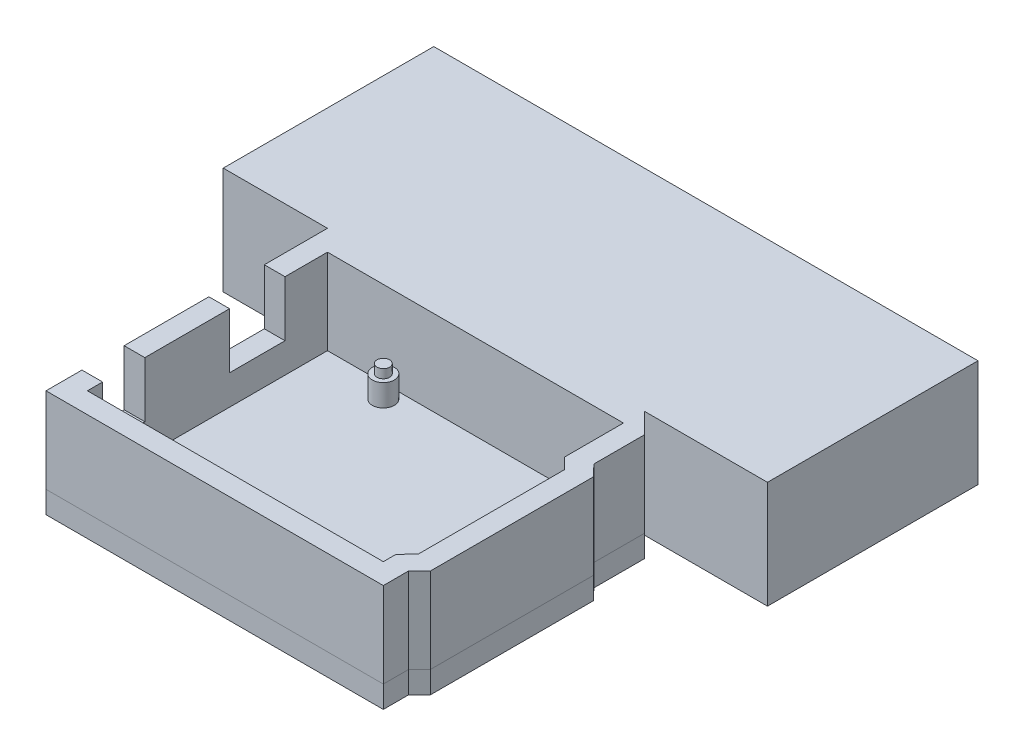
SolidWorks part; units mm, degrees
ref_plane "Front Plane" through (0, 0, 0) normal (0, 0, 1) x (1, 0, 0)
ref_plane "Top Plane" through (0, 0, 0) normal (0, 1, 0) x (1, 0, 0)
ref_plane "Right Plane" through (0, 0, 0) normal (1, 0, 0) x (0, 0, -1)
sketch "Sketch2" plane through (0, 0, 0) normal (0, 1, 0) x (1, 0, 0)
  line L3 (12.5897, 24.8031) -> (15.0697, 22.2631)
  line L4 (15.0697, 22.2631) -> (15.0697, -10.5029)
  line L5 (15.0697, -10.5029) -> (12.5897, -13.0429)
  line L6 (12.5897, -13.0429) -> (12.5897, -15.5829)
  line L7 (12.5897, -15.5829) -> (-53.4803, -15.5829)
  line L8 (-53.4803, -15.5829) -> (-53.4803, 37.7956)
  line L9 (-58.7803, 43.0956) -> (13.2202, 43.0956)
  line L10 (13.2202, 43.0956) -> (17.8897, 38.4261)
  line L11 (17.8897, 38.4261) -> (17.8897, 26.9614)
  line L12 (17.8897, 26.9614) -> (20.3697, 24.4214)
  line L13 (20.3697, 24.4214) -> (20.3697, -12.6612)
  line L14 (20.3697, -12.6612) -> (17.8897, -15.2012)
  line L15 (17.8897, -15.2012) -> (17.8897, -20.8829)
  line L16 (17.8897, -20.8829) -> (-58.7803, -20.8829)
  line L17 (-58.7803, -20.8829) -> (-58.7803, 43.0956)
  line L20 (12.5897, 37.7956) -> (12.5897, 24.8031)
  line L21 (11.0249, 37.7956) -> (12.5897, 36.2308) construction
  line L26 (12.5897, 36.2308) -> (12.5897, 24.8031) construction
  line L27 (-53.4803, 37.7956) -> (11.0249, 37.7956) construction
  line L28 (12.5897, 37.7956) -> (-53.4803, 37.7956)
  circle A0 centre (-38.2103, 35.2171) radius 1.5875
  circle A1 centre (12.5579, 19.9653) radius 1.5875
  circle A2 centre (12.5897, -7.9629) radius 1.5875
  circle A3 centre (-39.5103, -13.0429) radius 1.5875
  dimension "D4" = 3.5499
  dimension "D5" = 32.766
  dimension "D6" = 3.5499
  dimension "D7" = 2.54
  dimension "D8" = 66.07
  dimension "D9" = 53.3785
  dimension "D11" = 135.685
  dimension "D12" = 5.3
extrude "Boss-Extrude1" add sketch "Sketch2" along normal blind 5 contours L17 L16 L15 L14 L13 L12 L11 L10 L9 L7 L8 L3 L4 L5 L6 | L8 L7 L6 L5 L4 L3 A3 A2 A1 A0 region at (-19.6729, 0, -11.0012) region at (-22.7801, 0, -42.0778)
sketch "Sketch4" plane through (0, 5, 0) normal (0, 1, 0) x (1, 0, 0)
  line L3 (12.5885, 24.8065) -> (15.0685, 22.2665)
  line L4 (15.0685, 22.2665) -> (15.0685, -10.4995)
  line L5 (15.0685, -10.4995) -> (12.5885, -13.0395)
  line L6 (12.5885, -13.0395) -> (12.5885, -15.5795)
  line L7 (12.5885, -15.5795) -> (-53.4815, -15.5795)
  line L8 (-53.4815, -15.5795) -> (-53.4815, 37.799)
  line L9 (-58.7815, 43.099) -> (13.2191, 43.099)
  line L10 (13.2191, 43.099) -> (17.8885, 38.4295)
  line L11 (17.8885, 38.4295) -> (17.8885, 26.9649)
  line L12 (17.8885, 26.9649) -> (20.3685, 24.4249)
  line L13 (20.3685, 24.4249) -> (20.3685, -12.6578)
  line L14 (20.3685, -12.6578) -> (17.8885, -15.1978)
  line L15 (17.8885, -15.1978) -> (17.8885, -20.8795)
  line L16 (17.8885, -20.8795) -> (-58.7815, -20.8795)
  line L17 (-58.7815, -20.8795) -> (-58.7815, 43.099)
  line L21 (13.1885, 25.0509) -> (15.6685, 22.5109)
  line L22 (15.6685, 22.5109) -> (15.6685, -10.7438)
  line L23 (15.6685, -10.7438) -> (13.1885, -13.2838)
  line L24 (13.1885, -13.2838) -> (13.1885, -16.1795)
  line L25 (13.1885, -16.1795) -> (-54.0815, -16.1795)
  line L26 (-54.0815, -16.1795) -> (-54.0815, 38.399)
  line L31 (13.1885, 38.399) -> (13.1885, 25.0509)
  line L32 (11.2723, 38.399) -> (13.1885, 36.4827) construction
  line L33 (11.0238, 37.799) -> (12.5885, 36.2342) construction
  line L42 (13.1885, 36.4827) -> (13.1885, 25.0509) construction
  line L43 (-54.0815, 38.399) -> (11.2723, 38.399) construction
  line L44 (-53.4815, 37.799) -> (11.0238, 37.799) construction
  line L45 (12.5885, 36.2342) -> (12.5885, 24.8065) construction
  line L46 (12.5885, 24.8065) -> (12.5897, 37.7956)
  line L47 (12.5897, 37.7956) -> (-53.4815, 37.799)
  line L48 (-54.0815, 38.399) -> (13.1885, 38.399)
  circle A0 centre (-38.2115, 35.2205) radius 1.5875
  circle A1 centre (12.5567, 19.9688) radius 1.5875
  circle A2 centre (12.5885, -7.9595) radius 1.5875
  circle A3 centre (-39.5115, -13.0395) radius 1.5875
  dimension "D3" = 3.5499
  dimension "D4" = 32.766
  dimension "D5" = 3.5499
  dimension "D6" = 2.54
  dimension "D7" = 66.07
  dimension "D8" = 53.3785
  dimension "D10" = 135.685
  dimension "D11" = 0.6
extrude "Boss-Extrude3" add sketch "Sketch4" along normal blind 10 contours L9 L10 L11 L12 L13 L14 L15 L16 L17 | L21 L22 L23 L24 L25 L26 L48 L31
sketch "Sketch5" plane through (0, 15, 0) normal (0, 1, 0) x (1, 0, 0)
  line L0 (-58.7815, -20.8795) -> (-58.7815, 43.099) construction
  line L7 (-54.0815, -16.1795) -> (-54.0815, 38.399) construction
  line L14 (-58.7815, 28.439) -> (-58.7815, 16.439)
  line L16 (-54.0815, 28.439) -> (-54.0815, 16.439)
  line L17 (-54.0815, -16.1795) -> (-54.0815, 38.399) construction
  line L37 (-58.7815, 28.439) -> (-58.7815, 28.739)
  line L38 (-58.7815, 28.739) -> (-54.0815, 28.739)
  line L39 (-54.0815, 28.439) -> (-54.0815, 28.739)
  line L41 (-58.7815, 16.439) -> (-58.7815, 16.139)
  line L42 (-58.7815, 16.139) -> (-54.0815, 16.139)
  line L43 (-54.0815, 16.439) -> (-54.0815, 16.139)
  line L49 (-58.7815, -3.421) -> (-58.7815, -12.4107)
  line L59 (-54.0815, -3.421) -> (-54.0815, -12.4107)
  line L60 (-58.7815, -12.4107) -> (-58.7815, -12.7107)
  line L62 (-58.7815, -3.421) -> (-58.7815, -3.121)
  line L63 (-58.7815, -3.121) -> (-54.0815, -3.121)
  line L64 (-54.0815, -3.421) -> (-54.0815, -3.121)
  line L69 (-58.7815, -12.7107) -> (-54.0815, -12.7107)
  line L70 (-54.0815, -12.7107) -> (-54.0815, -12.4107)
  line L71 (-58.7815, -12.4107) -> (-58.7815, -12.7107)
  line M14 (-58.7815, 43.099) -> (-58.7815, -20.8795)
  line M32 (-54.0815, -16.1795) -> (-54.0815, 38.399)
  dimension "D1" = 0.3
  dimension "D2" = 12
  dimension "D3" = 0.3
  dimension "D4" = 0.3
  dimension "D6" = 0.3
extrude "Cut-Extrude1" cut sketch "Sketch5" against normal blind 3.22 contours L42 L38 M14 M32 | M32 M14 region at (-56.4315, 15, -22.439) region at (-56.4315, 15, 7.9158)
sketch "Sketch8" plane through (0, 15, 0) normal (0, 1, 0) x (1, 0, 0)
  line L1 (-54.0815, -16.1795) -> (-54.0815, -12.7107)
  line L11 (-58.7815, 16.139) -> (-54.0815, 16.139)
  line L17 (-58.7815, 16.139) -> (-58.7815, -3.121)
  line L18 (-58.7815, -3.121) -> (-54.0815, -3.121)
  line L20 (-54.0815, 16.139) -> (-54.0815, -3.121)
  line L30 (-54.0815, -12.7107) -> (-58.7815, -12.7107)
  line L31 (-58.7815, -12.7107) -> (-58.7815, -20.8795)
  line L62 (15.6685, 22.5109) -> (15.6685, -10.7438)
  line L63 (15.6685, -10.7438) -> (13.1885, -13.2838)
  line L64 (13.1885, -13.2838) -> (13.1885, -16.1795)
  line L65 (13.1885, -16.1795) -> (-54.0815, -16.1795)
  line L66 (-54.0815, -16.1795) -> (-54.0815, -12.7107) construction
  line L67 (-54.0815, -16.1795) -> (-54.0815, 38.399) construction
  line L71 (-58.7815, -20.8795) -> (17.8885, -20.8795)
  line L72 (17.8885, -20.8795) -> (17.8885, -15.1978)
  line L73 (17.8885, -15.1978) -> (20.3685, -12.6578)
  line L74 (20.3685, -12.6578) -> (20.3685, 24.4249)
  line L75 (20.3685, 24.4249) -> (17.8885, 26.9649)
  line L76 (17.8885, 26.9649) -> (17.8885, 38.4295)
  line L77 (17.8885, 38.4295) -> (13.2191, 43.099)
  line L78 (13.2191, 43.099) -> (-58.7815, 43.099)
  line L79 (-58.7815, 43.099) -> (-58.7815, 28.739)
  line L80 (-58.7815, 28.739) -> (-54.0815, 28.739)
  line L106 (-54.0815, 28.739) -> (-54.0815, 38.399)
  line L107 (-54.0815, 38.399) -> (13.1885, 38.399)
  line L109 (13.1885, 38.399) -> (13.1885, 25.0509)
  line L110 (13.1885, 25.0509) -> (15.6685, 22.5109)
extrude "Boss-Extrude4" add sketch "Sketch8" along normal blind 9.39
sketch "Sketch9" plane through (0, 5, 0) normal (0, 1, 0) x (1, 0, 0)
  circle A0 centre (-38.2103, 35.2171) radius 2.5
  circle A1 centre (12.5579, 19.9653) radius 2.5
  circle A2 centre (12.5897, -7.9629) radius 2.5
  circle A3 centre (-39.5103, -13.0429) radius 2.5
  dimension "D1" = 5
  dimension "D2" = 5
  dimension "D3" = 5
  dimension "D4" = 5
extrude "Boss-Extrude5" add sketch "Sketch9" along normal blind 5
sketch "Sketch10" plane through (0, 10, 0) normal (0, 1, 0) x (1, 0, 0)
  circle A0 centre (-38.2103, 35.2171) radius 1.44
  circle A1 centre (12.5579, 19.9653) radius 1.425
  circle A2 centre (12.5897, -7.9629) radius 1.425
  circle A3 centre (-39.5103, -13.0429) radius 1.425
  dimension "D1" = 2.88
  dimension "D2" = 2.85
  dimension "D3" = 2.85
  dimension "D4" = 2.85
extrude "Boss-Extrude6" add sketch "Sketch10" along normal blind 2
sketch "Sketch11" plane through (0, 11.78, 0) normal (0, 1, 0) x (1, 0, 0)
  line L5 (-58.7815, -3.121) -> (-54.0815, -3.121)
  line L6 (-58.7815, -3.121) -> (-58.7815, -12.7107)
  line L7 (-58.7815, -12.7107) -> (-54.0815, -12.7107)
  line L8 (-54.0815, -3.121) -> (-54.0815, -12.7107)
extrude "Cut-Extrude2" cut sketch "Sketch11" against normal blind 0.01
sketch "Sketch13" plane through (0, 24.39, 0) normal (0, 1, 0) x (1, 0, 0)
  line L0 (-58.7815, 16.139) -> (-58.7815, -3.121) construction
  line L1 (-58.7815, -3.121) -> (-54.0815, -3.121) construction
  line L2 (-54.0815, -3.121) -> (-54.0815, 16.139) construction
  line L3 (-54.0815, 16.139) -> (-58.7815, 16.139) construction
  line L4 (-54.0815, -12.7107) -> (-58.7815, -12.7107) construction
  line L5 (-58.7815, -12.7107) -> (-58.7815, -20.8795) construction
  line L6 (-58.7815, -20.8795) -> (17.8885, -20.8795) construction
  line L7 (17.8885, -20.8795) -> (17.8885, -15.1978) construction
  line L8 (17.8885, -15.1978) -> (20.3685, -12.6578) construction
  line L9 (20.3685, -12.6578) -> (20.3685, 24.4249) construction
  line L10 (20.3685, 24.4249) -> (17.8885, 26.9649) construction
  line L11 (17.8885, 26.9649) -> (17.8885, 38.4295) construction
  line L12 (17.8885, 38.4295) -> (13.2191, 43.099) construction
  line L13 (13.2191, 43.099) -> (-58.7815, 43.099) construction
  line L14 (-58.7815, 43.099) -> (-58.7815, 28.739) construction
  line L15 (-58.7815, 28.739) -> (-54.0815, 28.739) construction
  line L16 (-54.0815, 28.739) -> (-54.0815, 38.399) construction
  line L17 (-54.0815, 38.399) -> (13.1885, 38.399) construction
  line L18 (13.1885, 38.399) -> (13.1885, 25.0509) construction
  line L19 (13.1885, 25.0509) -> (15.6685, 22.5109) construction
  line L20 (15.6685, 22.5109) -> (15.6685, -10.7438) construction
  line L21 (15.6685, -10.7438) -> (13.1885, -13.2838) construction
  line L22 (13.1885, -13.2838) -> (13.1885, -16.1795) construction
  line L23 (13.1885, -16.1795) -> (-54.0815, -16.1795) construction
  line L24 (-54.0815, -16.1795) -> (-54.0815, -12.7107) construction
  line L25 (-58.7815, 16.139) -> (-58.7815, -3.121)
  line L26 (-58.7815, -3.121) -> (-54.0815, -3.121)
  line L27 (-54.0815, -3.121) -> (-54.0815, 16.139)
  line L28 (-54.0815, 16.139) -> (-58.7815, 16.139)
  line L29 (-54.0815, -12.7107) -> (-58.7815, -12.7107)
  line L30 (-58.7815, -12.7107) -> (-58.7815, -20.8795)
  line L31 (-58.7815, -20.8795) -> (17.8885, -20.8795)
  line L32 (17.8885, -20.8795) -> (17.8885, -15.1978)
  line L33 (17.8885, -15.1978) -> (20.3685, -12.6578)
  line L34 (20.3685, -12.6578) -> (20.3685, 24.4249)
  line L35 (20.3685, 24.4249) -> (17.8885, 26.9649)
  line L36 (17.8885, 26.9649) -> (17.8885, 38.4295)
  line L37 (17.8885, 38.4295) -> (13.2191, 43.099)
  line L38 (13.2191, 43.099) -> (-58.7815, 43.099)
  line L39 (-58.7815, 43.099) -> (-58.7815, 28.739)
  line L40 (-58.7815, 28.739) -> (-54.0815, 28.739)
  line L41 (-54.0815, 28.739) -> (-54.0815, 38.399)
  line L42 (-54.0815, 38.399) -> (13.1885, 38.399)
  line L43 (13.1885, 38.399) -> (13.1885, 25.0509)
  line L44 (13.1885, 25.0509) -> (15.6685, 22.5109)
  line L45 (15.6685, 22.5109) -> (15.6685, -10.7438)
  line L46 (15.6685, -10.7438) -> (13.1885, -13.2838)
  line L47 (13.1885, -13.2838) -> (13.1885, -16.1795)
  line L48 (13.1885, -16.1795) -> (-54.0815, -16.1795)
  line L49 (-54.0815, -16.1795) -> (-54.0815, -12.7107)
sketch "Sketch14" plane through (0, 0, 0) normal (0, 1, 0) x (1, 0, 0)
  line L1 (-82.4745, 43.099) -> (41.223, 43.099)
  line L2 (-82.4745, 43.099) -> (-82.4745, 90.9518)
  line L3 (-82.4745, 90.9518) -> (41.223, 90.9518)
  line L4 (41.223, 43.099) -> (41.223, 90.9518)
extrude "Boss-Extrude7" add sketch "Sketch14" along normal up to surface (24.39 mm away) up to face at (-11.5167, 24.39, -9.8301)
